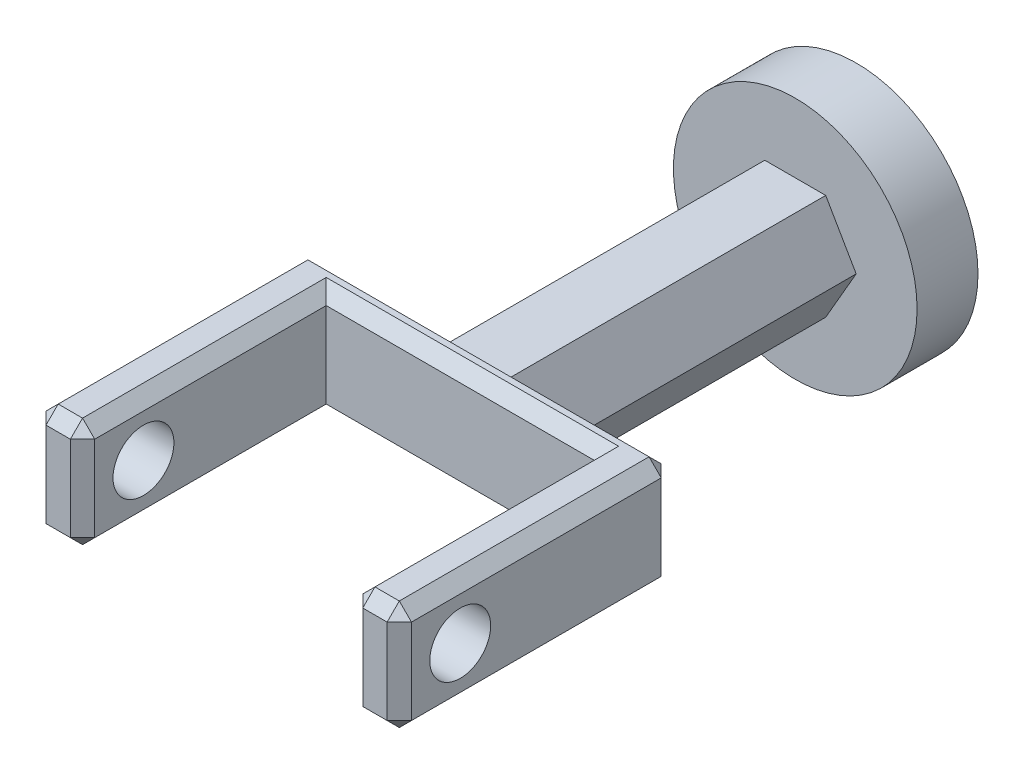
SolidWorks part; units mm, degrees
material "Aleación 1060"
ref_plane "Alzado" through (0, 0, 0) normal (0, 0, 1) x (1, 0, 0)
ref_plane "Planta" through (0, 0, 0) normal (0, 1, 0) x (1, 0, 0)
ref_plane "Vista lateral" through (0, 0, 0) normal (1, 0, 0) x (0, 0, -1)
sketch "Croquis1" plane through (0, 0, 0) normal (0, 0, 1) x (1, 0, 0)
  circle A0 centre (0, 0) radius 200
  dimension "D1" = 400
extrude "Saliente-Extruir1" add sketch "Croquis1" along normal blind 100
sketch "Croquis2" plane through (0, 0, 100) normal (0, 0, 1) x (1, 0, 0)
  line L1 (100, 0) -> (50, 86.6025)
  line L2 (50, 86.6025) -> (-50, 86.6025)
  line L3 (-50, 86.6025) -> (-100, 0)
  line L4 (-100, 0) -> (-50, -86.6025)
  line L5 (-50, -86.6025) -> (50, -86.6025)
  line L6 (50, -86.6025) -> (100, 0)
  circle A0 centre (0, 0) radius 86.6025 construction
  dimension "D1" = 100
extrude "Saliente-Extruir2" add sketch "Croquis2" along normal blind 500
sketch "Croquis3" plane through (0, 0, 600) normal (0, 0, 1) x (1, 0, 0)
  line L1 (-300, 90) -> (300, 90)
  line L2 (-300, 90) -> (-300, -90)
  line L3 (-300, -90) -> (300, -90)
  line L4 (300, 90) -> (300, -90)
  line L5 (-300, 90) -> (300, -90) construction
  line L6 (-300, -90) -> (300, 90) construction
  point P0 (0, 0)
  dimension "D1" = 180
  dimension "D2" = 600
extrude "Saliente-Extruir3" add sketch "Croquis3" along normal blind 50
sketch "Croquis4" plane through (0, 0, 650) normal (0, 0, 1) x (1, 0, 0)
  line L0 (300, 90) -> (-300, 90) construction
  line L1 (-300, -90) -> (-220, -90)
  line L2 (-300, -90) -> (-300, 90)
  line L3 (-300, 90) -> (-220, 90)
  line L4 (-220, -90) -> (-220, 90)
  line L6 (300, -90) -> (220, -90)
  line L7 (300, -90) -> (300, 90)
  line L8 (300, 90) -> (220, 90)
  line L9 (220, -90) -> (220, 90)
  dimension "D1" = 80
  dimension "D2" = 80
extrude "Saliente-Extruir4" add sketch "Croquis4" along normal blind 400
chamfer "Chaflán1" distance 20 angle 45 22 edges at (-220, 90, 850) (220, -90, 850) (-220, -90, 850) (-300, 90, 825) (-300, -90, 825) (300, 90, 825) (300, -90, 825) (-260, -90, 1050) (-220, 0, 1050) (-260, 90, 1050) (-300, 0, 1050) (260, 90, 1050) (220, 90, 850) (220, 0, 1050) (260, -90, 1050) (300, 0, 1050) (0, 90, 600) (0, -90, 600) (0, 90, 650) (-300, 0, 600) (0, -90, 650) (300, 0, 600)
sketch "Croquis5" plane through (300, 0, 0) normal (1, 0, 0) x (0, 0, -1)
  line L0 (0, 0) -> (-950, 0) construction
  circle A0 centre (-950, 0) radius 50
  dimension "D2" = 100
  dimension "D1" = 950
extrude "Cortar-Extruir1" cut sketch "Croquis5" against normal through all
